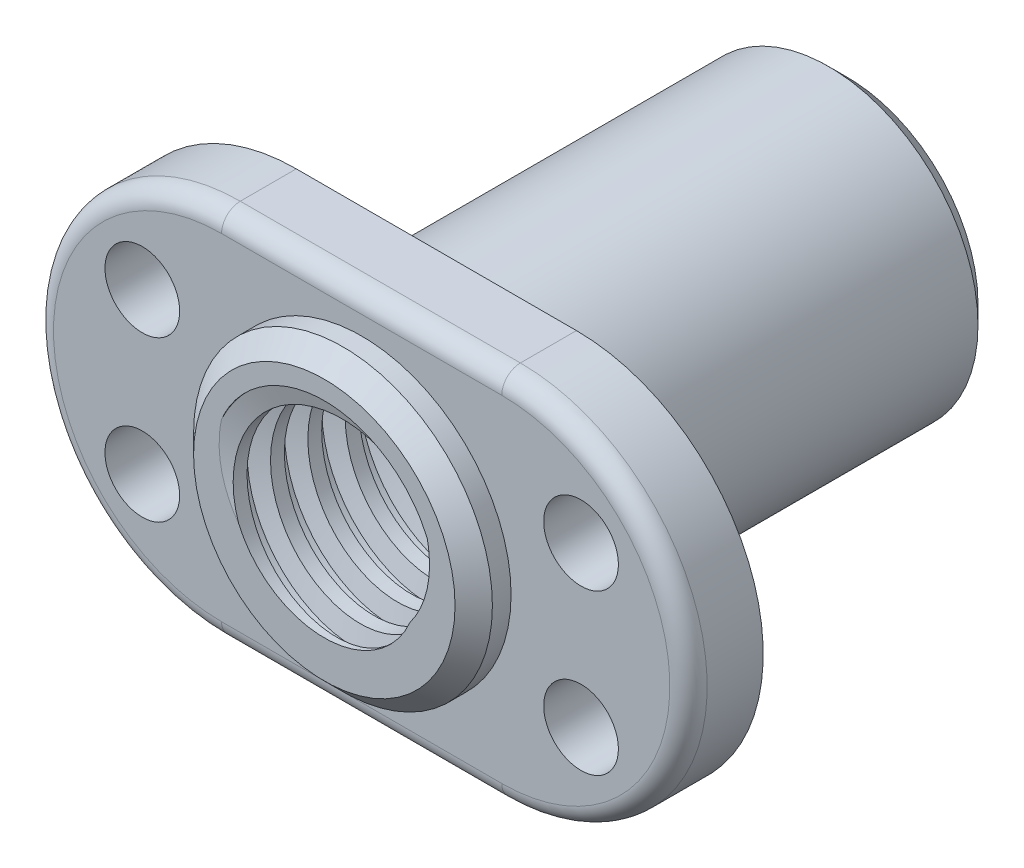
SolidWorks part; units mm, degrees
ref_plane "Alzado" through (0, 0, 0) normal (0, 0, 1) x (1, 0, 0)
ref_plane "Planta" through (0, 0, 0) normal (0, 1, 0) x (1, 0, 0)
ref_plane "Vista lateral" through (0, 0, 0) normal (1, 0, 0) x (0, 0, -1)
sketch "Croquis1" plane through (0, 0, 0) normal (0, 0, 1) x (1, 0, 0)
  line L0 (-7.5, 0) -> (7.5, 0) construction
  line L1 (-7.5, 0) -> (7.5, 0) construction
  line L2 (-7.5, 10) -> (7.5, 10)
  line L3 (-7.5, -10) -> (7.5, -10)
  arc A0 (-7.5, 10) -> (-7.5, -10) centre (-7.5, 0) ccw
  arc A1 (7.5, -10) -> (7.5, 10) centre (7.5, 0) ccw
  circle A2 centre (0, 0) radius 5
  point P0 (0, 0)
  point P4 (0, 0)
  dimension "D2" = 10
  dimension "D3" = 10
  dimension "D1" = 15
extrude "Saliente-Extruir1" add sketch "Croquis1" along normal blind 4
sketch "Croquis2" plane through (0, 0, 0) normal (0, 0, -1) x (-1, 0, 0)
  circle A0 centre (0, 0) radius 5 construction
  circle A1 centre (0, 0) radius 5
  circle A2 centre (0, 0) radius 8
  dimension "D1" = 3
extrude "Saliente-Extruir2" add sketch "Croquis2" along normal blind 22 and the other way blind 6
fillet "Redondeo1" radius 1 5 edges at (0, -10, 4) (-17.5, 0, 4) (0, 10, 4) (8, 0, 0) (17.5, 0, 4)
chamfer "Chaflán1" distance 1 angle 45 1 edges at (-8, 0, -22)
chamfer "Chaflán2" distance 1 angle 45 1 edges at (-8, 0, 6)
sketch "Croquis3" plane through (0, 0, 6) normal (0, 0, 1) x (1, 0, 0)
  circle A0 centre (0, 0) radius 5 construction
  circle A1 centre (0, 0) radius 5
curve "Hélice/Espiral1" pitch 2 height 28 radius 5 centre (0, 0, 6) axis (0, 0, -1) start towards (0, 1, 0)
sketch "Croquis4" plane through (0, 0, 0) normal (1, 0, 0) x (0, 0, -1)
  line L0 (-10.1959, 5) -> (5.9117, 5) construction
  line L1 (-6, 9.115) -> (-6, -2.67) construction
  line L2 (-6.6293, 5) -> (-5.3707, 5)
  line L3 (-5.3707, 5) -> (-5.6293, 6)
  line L4 (-6, 5) -> (-6, 6) construction
  line L5 (-6.3707, 6) -> (-5.6293, 6)
  line L6 (-6.3707, 6) -> (-6.6293, 5)
  point P5 (-5.5, 5.5)
  point P8 (-6, 5)
  point P14 (-6, 6)
  point P18 (-6.5, 5.5)
  dimension "D1" = 5
  dimension "D2" = 6
  dimension "D3" = 1
  dimension "D4" = 14.5
  dimension "D5" = 1
sweep "Cortar-Barrer1" cut profiles "Croquis4" path "Hélice/Espiral1" align with end faces yes
sketch "Croquis5" plane through (0, 0, 4) normal (0, 0, 1) x (1, 0, 0)
  line L0 (-24.418, 0) -> (20.9104, 0) construction
  line L1 (-11.7462, 4.2753) -> (0, 0) construction
  line L2 (0, 0) -> (0, 11.6515) construction
  circle A0 centre (0, 0) radius 12.5 construction
  circle A1 centre (-11.7462, 4.2753) radius 2
  circle A2 centre (-11.7462, -4.2753) radius 2
  circle A3 centre (11.7462, -4.2753) radius 2
  circle A4 centre (11.7462, 4.2753) radius 2
  dimension "D1" = 25
  dimension "D2" = 4
  dimension "D3" = 20
extrude "Cortar-Extruir1" cut sketch "Croquis5" against normal up to surface (4 mm away) up to face at (9, 0, 0)
